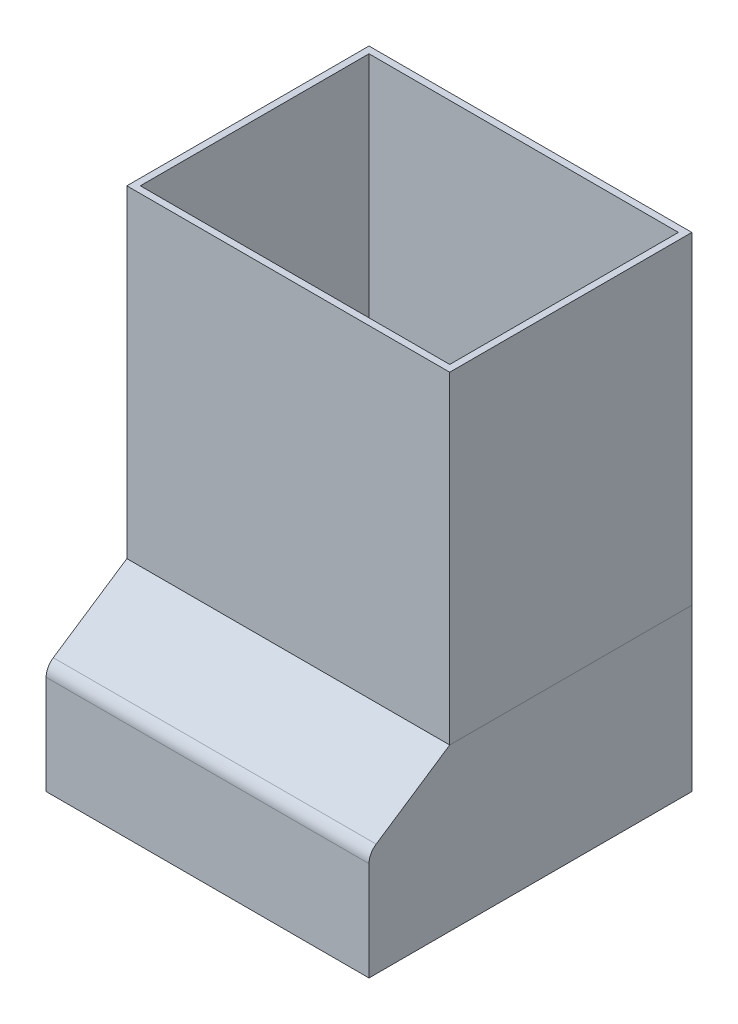
SolidWorks part; units mm, degrees
ref_plane "Front Plane" through (0, 0, 0) normal (0, 0, 1) x (1, 0, 0)
ref_plane "Top Plane" through (0, 0, 0) normal (0, 1, 0) x (1, 0, 0)
ref_plane "Right Plane" through (0, 0, 0) normal (1, 0, 0) x (0, 0, -1)
sketch "Sketch1" plane through (0, 0, 0) normal (0, 1, 0) x (1, 0, 0)
  line L0 (-304.8, 0) -> (304.8, 0) construction
  line L1 (-304.8, 304.8) -> (304.8, 304.8)
  line L2 (-304.8, 304.8) -> (-304.8, -304.8)
  line L3 (-304.8, -304.8) -> (304.8, -304.8)
  line L4 (304.8, 304.8) -> (304.8, -304.8)
  line L5 (-304.8, -304.8) -> (304.8, -304.8) construction
  point P6 (0, 0)
  point P7 (-260.9278, -304.8)
  dimension "D1" = 609.6
  dimension "D2" = 609.6
extrude "Boss-Extrude1" add sketch "Sketch1" along normal blind 304.8 contours L2 L1 L4 L3
sketch "Sketch9" plane through (0, 304.8, 0) normal (0, 1, 0) x (1, 0, 0)
  line L0 (-304.8, -152.4) -> (304.8, -152.4) construction
  line L1 (-304.8, 304.8) -> (-304.8, -304.8) construction
  line L2 (304.8, 304.8) -> (304.8, -304.8) construction
  line L3 (-304.8, -304.8) -> (304.8, -304.8) construction
  dimension "D1" = 152.4
sketch "Sketch10" plane through (0, 0, 304.8) normal (0, 0, 1) x (1, 0, 0)
  line L0 (-304.8, 203.2) -> (304.8, 203.2) construction
  line L1 (-304.8, 304.8) -> (-304.8, 0) construction
  line L2 (304.8, 304.8) -> (304.8, 0) construction
  line L3 (-304.8, 0) -> (304.8, 0) construction
  dimension "D1" = 203.2
sketch "Sketch11" plane through (304.8, 0, 0) normal (1, 0, 0) x (0, 0, -1)
  line L0 (-304.8, 203.2) -> (-152.4, 304.8)
extrude "Cut-Extrude2" cut sketch "Sketch11" against normal blind 609.6 and the other way through all contours L0
shell "Shell11" thickness 12.7
sketch "Sketch13" plane through (0, 304.8, 0) normal (0, 1, 0) x (1, 0, 0)
  line L0 (-304.8, 304.8) -> (-304.8, -152.4)
  line L1 (-304.8, -152.4) -> (304.8, -152.4)
  line L2 (304.8, -152.4) -> (304.8, 304.8)
  line L3 (304.8, 304.8) -> (-304.8, 304.8)
extrude "Boss-Extrude7" add sketch "Sketch13" along normal blind 609.6 separate body
shell "Shell13" thickness 12.7 removed face at (0, 914.4, -76.2)
sketch "Sketch14" plane through (0, 317.5, 0) normal (0, 1, 0) x (1, 0, 0)
  line L0 (-292.1, -38.1) -> (-165.1, -38.1)
  line L1 (-292.1, 292.1) -> (-292.1, -139.7) construction
  line L2 (-165.1, -38.1) -> (-165.1, -139.7)
  line L3 (-292.1, -139.7) -> (292.1, -139.7) construction
  line L4 (-165.1, -139.7) -> (-292.1, -139.7)
  line L5 (-292.1, -139.7) -> (-292.1, -38.1)
  dimension "D1" = 127
  dimension "D2" = 101.6
extrude "Boss-Extrude8" add sketch "Sketch14" along normal blind 152.4
shell "Shell14" thickness 12.7 removed face at (-228.6, 469.9, 88.9)
sketch "Sketch17" plane through (0, 317.5, 0) normal (0, 1, 0) x (1, 0, 0)
  line L1 (-292.1, -50.8) -> (-177.8, -50.8)
  line L2 (-292.1, -50.8) -> (-292.1, -139.7)
  line L3 (-292.1, -139.7) -> (-177.8, -139.7)
  line L4 (-177.8, -50.8) -> (-177.8, -139.7)
  point P0 (-177.8, -50.8)
extrude "Cut-Extrude3" cut sketch "Sketch17" against normal blind 237.744
fillet "Fillet2" radius 30.32 1 edges at (0, 203.2, 304.8)
sketch "Sketch18" plane through (0, 317.5, 0) normal (0, 1, 0) x (1, 0, 0)
  line L0 (-292.1, -50.8) -> (-304.8, -50.8) construction
  line L1 (-304.8, 304.8) -> (-304.8, -304.8) construction
